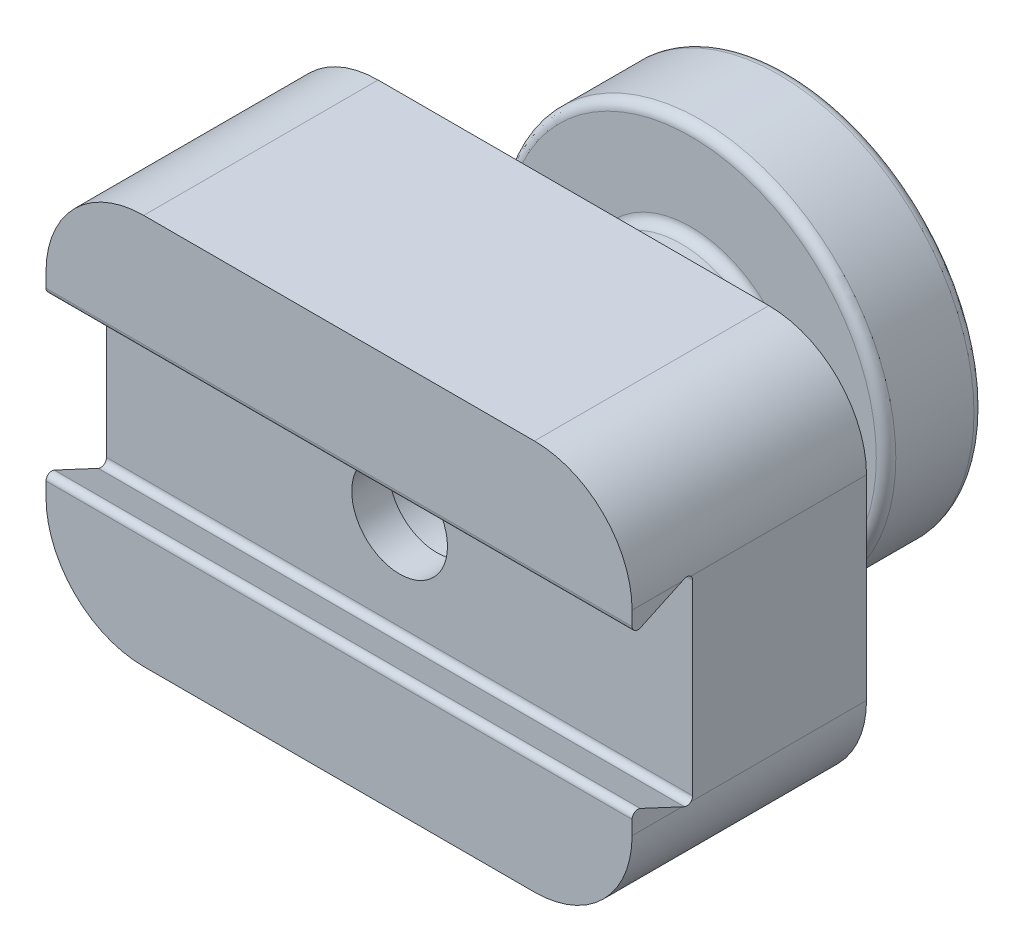
SolidWorks part; units mm, degrees
ref_plane "Front" through (0, 0, 0) normal (0, 0, 1) x (1, 0, 0)
ref_plane "Top" through (0, 0, 0) normal (0, 1, 0) x (1, 0, 0)
ref_plane "Right" through (0, 0, 0) normal (1, 0, 0) x (0, 0, -1)
sketch "Sketch1" plane through (0, 0, 0) normal (0, 0, 1) x (1, 0, 0)
  line L0 (18.3647, 0) -> (-19.4746, 0) construction
  arc A1 (10, 0) -> (-10, 0) centre (0, 0) ccw
  arc A2 (10, 0) -> (-10, 0) centre (0, 0) cw
  point P4 (0, -2.5)
  dimension "D2" = 10
extrude "Boss-Extrude1" add sketch "Sketch1" along normal blind 5
sketch "Sketch2" plane through (0, 0, 0) normal (0, 0, 1) x (1, 0, 0)
  circle A0 centre (0, 0) radius 5
  dimension "D1" = 10
extrude "Boss-Extrude2" add sketch "Sketch2" along normal blind 11
ref_plane "Plane1" through (0, 0, 11) normal (0, 0, 1) x (1, 0, 0)
ref_point "Point1"
sketch "Sketch3" plane through (0, 0, 11) normal (0, 0, 1) x (1, 0, 0)
  line L1 (-15, 10) -> (15, 10)
  line L2 (-15, 10) -> (-15, -10)
  line L3 (-15, -10) -> (15, -10)
  line L4 (15, 10) -> (15, -10)
  line L5 (-15, 10) -> (15, -10) construction
  line L6 (-15, -10) -> (15, 10) construction
  point P0 (0, 0)
  dimension "D1" = 20
  dimension "D2" = 30
  dimension "D6" = 30
extrude "Boss-Extrude3" add sketch "Sketch3" along normal blind 12
ref_plane "Plane2" through (-10, 0, 0) normal (1, 0, 0) x (0, 0, -1)
sketch "Sketch5" plane through (-10, 0, 0) normal (1, 0, 0) x (0, 0, -1)
  line L0 (-23, 3.8044) -> (-19.9, 5.25)
  line L2 (-19.9, 5.25) -> (-19.9, -5.25)
  line L3 (-19.9, -5.25) -> (-23, -3.8044)
  line L4 (-23, -3.8044) -> (-23, 3.8044)
  line L5 (-23, 0) -> (-19.9, 0) construction
  line L7 (-23, 10) -> (-23, -10) construction
  line L8 (-23, 10) -> (-11, 10) construction
  line L9 (-23, -10) -> (-23, 10) construction
  dimension "D1" = 10.5
  dimension "D2" = 10
  dimension "D3" = 3.1
  dimension "D4" = 5.25
  dimension "D5" = 3.1
  dimension "D6" = 3.8044
  dimension "D8" = 65
extrude "Cut-Extrude1" cut sketch "Sketch5" along normal through all both and the other way through all
sketch "Sketch6" plane through (0, 0, 23) normal (0, 0, 1) x (1, 0, 0)
  circle A0 centre (0, 0) radius 2.45
  dimension "D1" = 4.9
extrude "Cut-Extrude2" cut sketch "Sketch6" against normal blind 5
pattern_linear "LPattern1" [suppressed] count 3 spacing 7 of bodies 105
fillet "Fillet1" radius 0.3 4 edges at (0, -5.25, 19.9) (0, -3.8044, 23) (0, 5.25, 19.9) (0, 3.8044, 23)
fillet "Fillet2" radius 5 4 edges at (-15, -10, 17) (15, -10, 17) (15, 10, 17) (-15, 10, 17)
fillet "Fillet3" radius 0.5 4 edges at (10, 0, 0) (-10, 0, 5) (-5, 0, 5) (5, 0, 11)
sketch "Sketch7" plane through (0, 0, 18) normal (0, 0, 1) x (1, 0, 0)
  circle A0 centre (0, 0) radius 2.9
  dimension "D1" = 5.8
extrude "Cut-Extrude3" cut sketch "Sketch7" against normal blind 6
